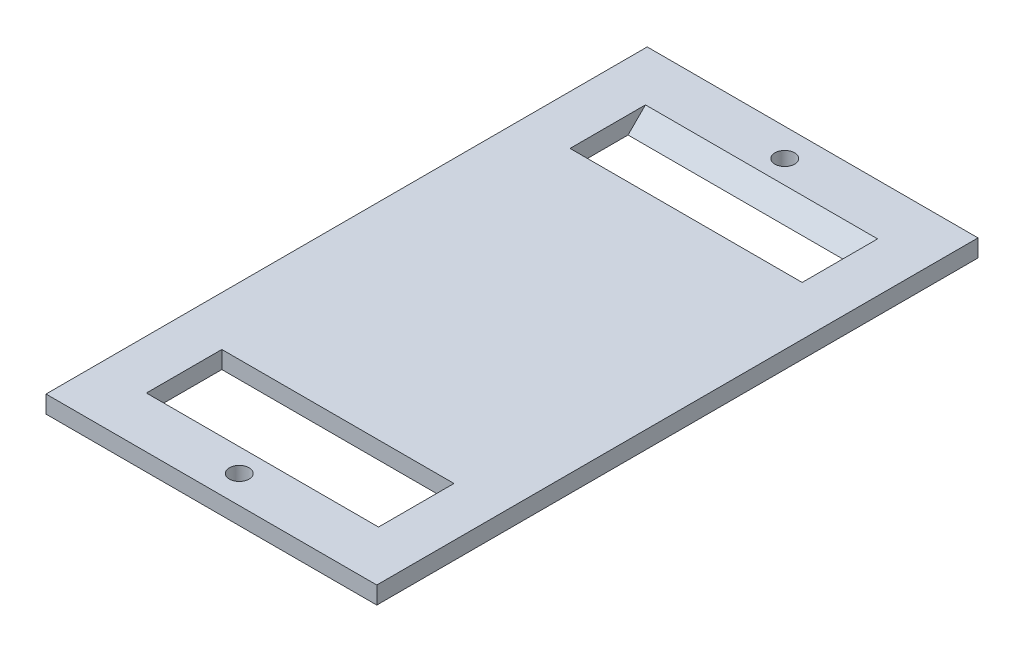
SolidWorks part; units mm, degrees
ref_plane "前视基准面" through (0, 0, 0) normal (0, 0, 1) x (1, 0, 0)
ref_plane "上视基准面" through (0, 0, 0) normal (0, 1, 0) x (1, 0, 0)
ref_plane "右视基准面" through (0, 0, 0) normal (1, 0, 0) x (0, 0, -1)
sketch "草图1" plane through (0, 0, 0) normal (0, 1, 0) x (1, 0, 0)
  line L1 (-28.5, 51.8) -> (28.5, 51.8)
  line L2 (-28.5, 51.8) -> (-28.5, -51.8)
  line L3 (-28.5, -51.8) -> (28.5, -51.8)
  line L4 (28.5, 51.8) -> (28.5, -51.8)
  line L5 (-28.5, 51.8) -> (28.5, -51.8) construction
  line L6 (-28.5, -51.8) -> (28.5, 51.8) construction
  circle A0 centre (0, 47) radius 1.7
  circle A1 centre (0, -47) radius 1.7
  point P0 (0, 0)
  dimension "D3" = 47
  dimension "D4" = 47
  dimension "D5" = 3.4
  dimension "D6" = 3.4
  dimension "D1" = 57
  dimension "D2" = 103.6
extrude "凸台-拉伸1" add sketch "草图1" along normal blind 3
sketch "草图2" plane through (0, 3, 0) normal (0, 1, 0) x (1, 0, 0)
  line L0 (0, 52.6523) -> (0, -54.7405) construction
  line L2 (-20, 40) -> (20, 40)
  line L3 (-20, 40) -> (-20, 30)
  line L4 (-20, 30) -> (20, 30)
  line L5 (20, 40) -> (20, 30)
  line L6 (-20, 40) -> (20, 30) construction
  line L7 (-20, 30) -> (20, 40) construction
  line L8 (-20, -30) -> (20, -30)
  line L9 (-20, -30) -> (-20, -40)
  line L10 (-20, -40) -> (20, -40)
  line L11 (20, -30) -> (20, -40)
  line L12 (-20, -30) -> (20, -40) construction
  line L13 (-20, -40) -> (20, -30) construction
  point P3 (0, 35)
  point P8 (0, -35)
  dimension "D1" = 40
  dimension "D2" = 40
  dimension "D3" = 10
  dimension "D4" = 10
  dimension "D5" = 40
  dimension "D6" = 40
extrude "切除-拉伸1" cut sketch "草图2" against normal blind 3
chamfer "倒角1" distance 3 angle 45 2 edges at (0, 3, 40) (0, 3, -40)
